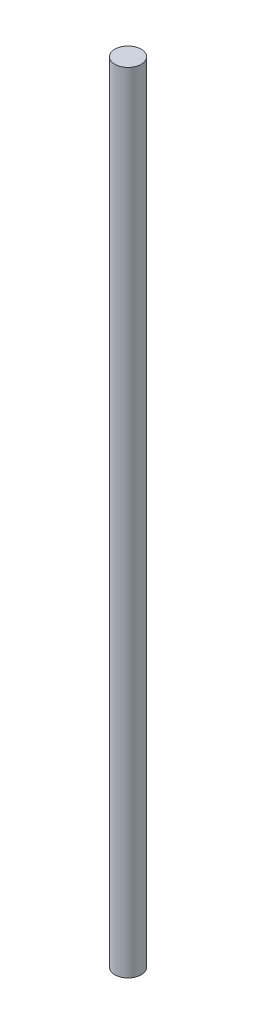
SolidWorks part; units mm, degrees
ref_plane "Plan de face" through (0, 0, 0) normal (0, 0, 1) x (1, 0, 0)
ref_plane "Plan de dessus" through (0, 0, 0) normal (0, 1, 0) x (1, 0, 0)
ref_plane "Plan de droite" through (0, 0, 0) normal (1, 0, 0) x (0, 0, -1)
sketch "Esquisse1" plane through (0, 0, 0) normal (0, 1, 0) x (1, 0, 0)
  circle A0 centre (0, 0) radius 1.5
  dimension "D1" = 3
extrude "Boss.-Extru.1" add sketch "Esquisse1" along normal blind 90
